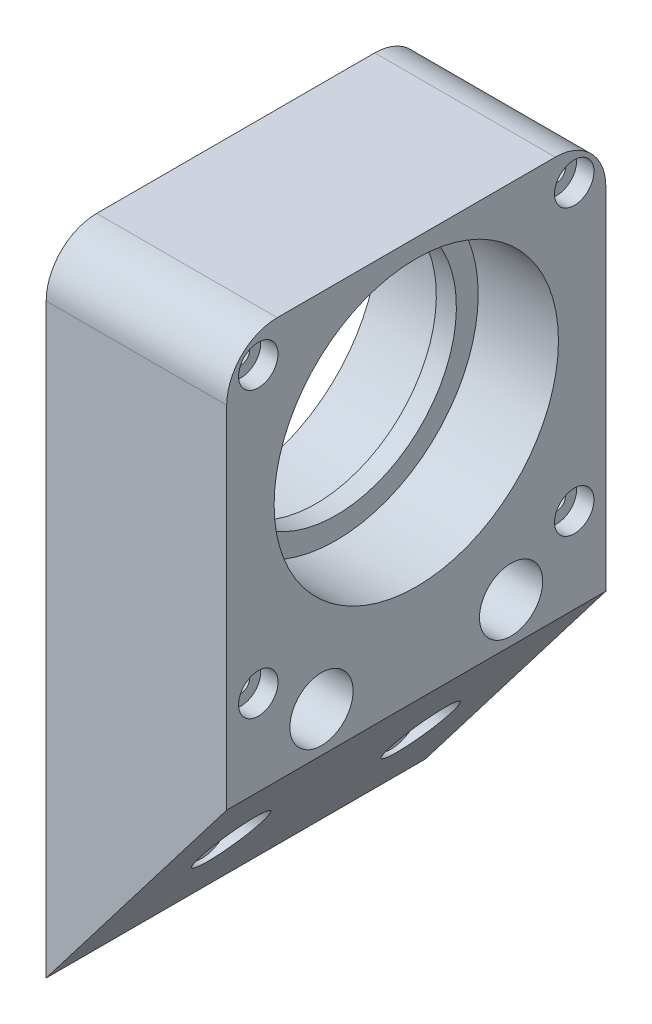
SolidWorks part; units mm, degrees
ref_plane "Front Plane" through (0, 0, 0) normal (0, 0, 1) x (1, 0, 0)
ref_plane "Top Plane" through (0, 0, 0) normal (0, 1, 0) x (1, 0, 0)
ref_plane "Right Plane" through (0, 0, 0) normal (1, 0, 0) x (0, 0, -1)
sketch "Sketch1" plane through (0, 0, 0) normal (0, 0, 1) x (1, 0, 0)
  line L0 (381, 457.2) -> (438.15, 457.2)
  line L1 (438.15, 457.2) -> (438.15, 431.8)
  line L2 (381, 457.2) -> (381, 357.2)
  line L5 (381, 357.2) -> (438.15, 431.8)
  dimension "D1" = 57.15
  dimension "D2" = 100
extrude "Boss-Extrude1" add sketch "Sketch1" along normal blind 120
sketch "Sketch3" plane through (438.15, 0, 0) normal (1, 0, 0) x (0, 0, -1)
  line L1 (-120, 431.8) -> (0, 431.8)
  line L2 (-120, 431.8) -> (-120, 357.2)
  line L3 (-120, 357.2) -> (0, 357.2)
  line L4 (0, 431.8) -> (0, 357.2)
  circle A0 centre (-90, 394.5) radius 4.25
  circle A1 centre (-30, 394.5) radius 4.25
  circle A2 centre (-90, 444.5) radius 4.25
  circle A3 centre (-30, 444.5) radius 4.25
  dimension "D1" = 30
  dimension "D2" = 30
  dimension "D3" = 37.3
  dimension "D4" = 37.3
extrude "Cut-Extrude1" cut sketch "Sketch3" against normal blind 120 contours A1 | A0
sketch "Sketch5" plane through (438.15, 0, 0) normal (1, 0, 0) x (0, 0, -1)
  circle A0 centre (-90, 394.5) radius 10
  circle A1 centre (-30, 394.5) radius 10
  circle A2 centre (-90, 444.5) radius 10
  circle A3 centre (-30, 444.5) radius 10
extrude "Cut-Extrude2" cut sketch "Sketch5" against normal blind 38
sketch "Sketch6" plane through (438.15, 0, 0) normal (1, 0, 0) x (0, 0, -1)
  circle A0 centre (-90, 444.5) radius 4.25
  circle A1 centre (-30, 444.5) radius 4.25
extrude "Cut-Extrude3" cut sketch "Sketch6" against normal blind 103
sketch "Sketch7" plane through (0, 457.2, 0) normal (0, 1, 0) x (1, 0, 0)
  line L1 (381, 0) -> (438.15, 0)
  line L2 (381, 0) -> (381, -120)
  line L3 (381, -120) -> (438.15, -120)
  line L4 (438.15, 0) -> (438.15, -120)
extrude "Boss-Extrude2" add sketch "Sketch7" along normal blind 101.6
fillet "Fillet1" radius 16 2 edges at (409.575, 558.8, 0) (409.575, 558.8, 120)
sketch "Sketch8" plane through (381, 0, 0) normal (-1, 0, 0) x (0, 0, 1)
  line L0 (120, 457.2) -> (0, 457.2)
  line L1 (120, 542.8) -> (120, 357.2) construction
  line L2 (0, 542.8) -> (0, 357.2) construction
  line L3 (16, 558.8) -> (104, 558.8) construction
  circle A0 centre (60, 508) radius 45
  dimension "D1" = 101.6
  dimension "D2" = 50.8
extrude "Cut-Extrude4" cut sketch "Sketch8" against normal blind 25.4 contours A0 region at (381, 508, 60)
sketch "Sketch9" plane through (438.15, 0, 0) normal (1, 0, 0) x (0, 0, -1)
  line L0 (-104, 558.8) -> (-16, 558.8) construction
  circle A0 centre (-60, 508) radius 45
  dimension "D1" = 50.8
extrude "Cut-Extrude5" cut sketch "Sketch9" against normal blind 25.4
sketch "Sketch10" plane through (438.15, 0, 0) normal (1, 0, 0) x (0, 0, -1)
  circle A0 centre (-60, 508) radius 38.1
extrude "Cut-Extrude6" cut sketch "Sketch10" against normal blind 76.2
sketch "Sketch11" plane through (438.15, 0, 0) normal (1, 0, 0) x (0, 0, -1)
  line L0 (-120, 431.8) -> (-120, 542.8) construction
  line L1 (-110, 548.8) -> (-10, 548.8)
  line L2 (-110, 548.8) -> (-110, 458.8)
  line L3 (-110, 458.8) -> (-10, 458.8)
  line L4 (-10, 548.8) -> (-10, 458.8)
  line L5 (0, 431.8) -> (0, 542.8) construction
  line L6 (-104, 558.8) -> (-16, 558.8) construction
  circle A1 centre (-110, 548.8) radius 2.75
  circle A2 centre (-10, 548.8) radius 2.75
  circle A3 centre (-10, 458.8) radius 2.75
  circle A4 centre (-110, 458.8) radius 2.75
  dimension "D1" = 10
  dimension "D2" = 10
  dimension "D3" = 10
  dimension "D4" = 90
extrude "Cut-Extrude7" cut sketch "Sketch11" against normal blind 84.4 contours L1 A1 L2 | L2 A1 L1 | L4 A2 L1 | L1 A2 L4 | L3 A3 L4 | L4 A3 L3 | L2 A4 L3 | L3 A4 L2 region at (438.15, 549.189, 110.389) region at (438.15, 547.6329, 108.8329) region at (438.15, 549.189, 9.611) region at (438.15, 547.6329, 11.1671) region at (438.15, 459.9671, 108.8329) region at (438.15, 458.411, 110.389) region at (438.15, 458.411, 9.611) region at (438.15, 459.9671, 11.1671)
sketch "Sketch12" plane through (438.15, 0, 0) normal (1, 0, 0) x (0, 0, -1)
  circle A0 centre (-110, 548.8) radius 6.25
  circle A1 centre (-10, 548.8) radius 6.25
  circle A2 centre (-10, 458.8) radius 6.25
  circle A3 centre (-110, 458.8) radius 6.25
extrude "Cut-Extrude8" cut sketch "Sketch12" against normal blind 5.5
